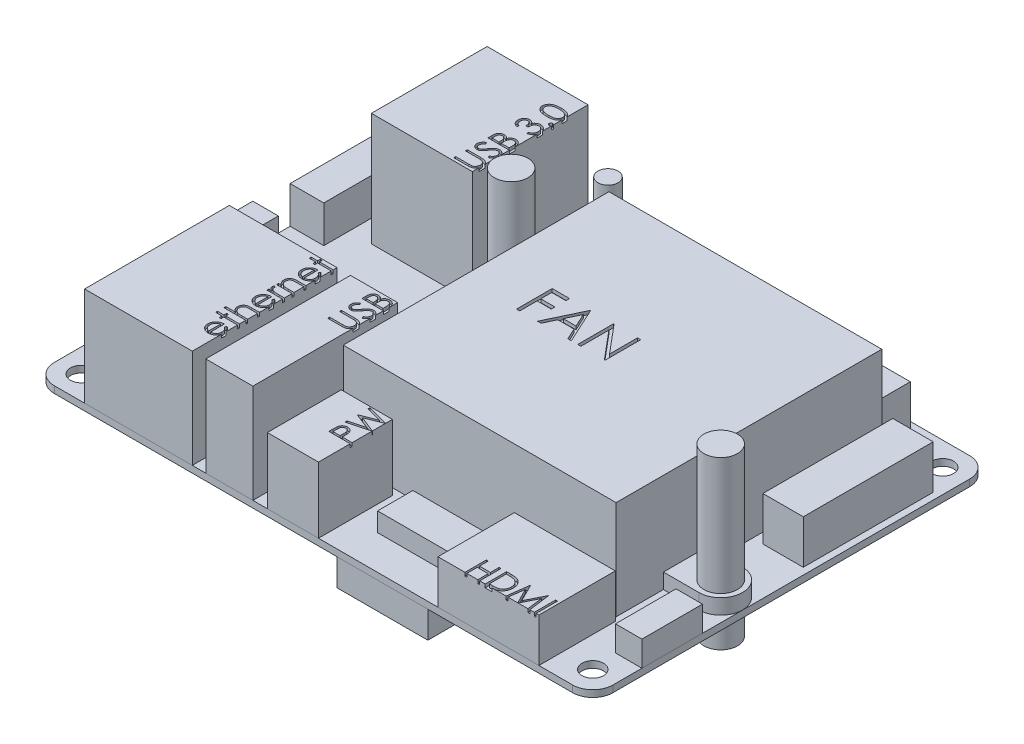
SolidWorks part; units mm, degrees
material "Silicon"
ref_plane "Front Plane" through (0, 0, 0) normal (0, 0, 1) x (1, 0, 0)
ref_plane "Top Plane" through (0, 0, 0) normal (0, 1, 0) x (1, 0, 0)
ref_plane "Right Plane" through (0, 0, 0) normal (1, 0, 0) x (0, 0, -1)
sketch "Sketch1" plane through (0, 0, 0) normal (0, 1, 0) x (1, 0, 0)
  line L1 (-38.5, -29.5) -> (38.5, -29.5)
  line L2 (-41.5, -26.5) -> (-41.5, 26.5)
  line L3 (-38.5, 29.5) -> (38.5, 29.5)
  line L4 (41.5, -26.5) -> (41.5, 26.5)
  line L5 (-41.5, -29.5) -> (41.5, 29.5) construction
  line L6 (-41.5, 29.5) -> (41.5, -29.5) construction
  arc A0 (38.5, 29.5) -> (41.5, 26.5) centre (38.5, 26.5) cw
  arc A1 (38.5, -29.5) -> (41.5, -26.5) centre (38.5, -26.5) ccw
  arc A2 (-38.5, -29.5) -> (-41.5, -26.5) centre (-38.5, -26.5) cw
  arc A3 (-41.5, 26.5) -> (-38.5, 29.5) centre (-38.5, 26.5) cw
  point P0 (0, 0)
  dimension "D3" = 3
  dimension "D1" = 83
  dimension "D2" = 59
extrude "PCB Extrude" add sketch "Sketch1" against normal blind 1
ref_plane "Plane_UnderSurface" through (0, -0.1, 0) normal (0, 1, 0) x (1, 0, 0)
ref_plane "Plane_AboveTop" through (0, 1, 0) normal (0, 1, 0) x (1, 0, 0)
sketch "IMAGE_TOP_PADS" plane through (0, 1, 0) normal (0, 1, 0) x (1, 0, 0)
  line L0 (-47.2752, 1.0682) -> (46.7248, 1.0682) construction
  line L2 (-41.5535, -29.5341) -> (41.4465, -29.5341) construction
  line L31 (-40.884, -25.1069) -> (-40.884, 27.8931) construction
  dimension "D1" = 53
  dimension "D2" = 83
sketch "IMAGE_TOP_COMPONENTS" plane through (0, 1, 0) normal (0, 1, 0) x (1, 0, 0)
  line L0 (-41.4491, -26.8822) -> (41.5509, -26.8822) construction
  dimension "D1" = 83
sketch "IMAGE_BOTTOM_COMPONENTS" plane through (0, -1, 0) normal (0, -1, 0) x (1, 0, 0)
  line L0 (-41.5726, -13.5939) -> (41.4274, -13.5939) construction
  dimension "D1" = 83
sketch "Sketch3" plane through (0, 0, 0) normal (0, 1, 0) x (1, 0, 0)
  line L0 (-38, -26) -> (38, -26) construction
  line L1 (-38, -26) -> (-38, 26) construction
  line L4 (38.5, 29.5) -> (-38.5, 29.5)
  line L5 (-41.5, 26.5) -> (-41.5, -26.5)
  line L6 (-38.5, -29.5) -> (38.5, -29.5)
  line L7 (41.5, -26.5) -> (41.5, 26.5)
  line L8 (38.5, 29.5) -> (-38.5, 29.5) construction
  line L9 (-41.5, 26.5) -> (-41.5, -26.5) construction
  line L10 (-38.5, -29.5) -> (38.5, -29.5) construction
  line L11 (41.5, -26.5) -> (41.5, 26.5) construction
  circle A0 centre (-12.8308, 12.7046) radius 1.6
  circle A1 centre (38.2313, -7.2227) radius 1.6
  circle A2 centre (-38, 26) radius 1.6
  circle A4 centre (38, 26) radius 1.6
  circle A6 centre (38, -26) radius 1.6
  arc A7 (41.5, 26.5) -> (38.5, 29.5) centre (38.5, 26.5) ccw
  circle A8 centre (-38, -26) radius 1.6
  arc A9 (-38.5, 29.5) -> (-41.5, 26.5) centre (-38.5, 26.5) ccw
  arc A10 (-41.5, -26.5) -> (-38.5, -29.5) centre (-38.5, -26.5) ccw
  arc A11 (38.5, -29.5) -> (41.5, -26.5) centre (38.5, -26.5) ccw
  arc A12 (41.5, 26.5) -> (38.5, 29.5) centre (38.5, 26.5) ccw construction
  arc A13 (-38.5, 29.5) -> (-41.5, 26.5) centre (-38.5, 26.5) ccw construction
  arc A14 (-41.5, -26.5) -> (-38.5, -29.5) centre (-38.5, -26.5) ccw construction
  arc A15 (38.5, -29.5) -> (41.5, -26.5) centre (38.5, -26.5) ccw construction
  point P0 (0, -26)
  point P6 (-38, 0)
  dimension "D1" = 3.2
  dimension "D2" = 52
  dimension "D3" = 76
  dimension "D4" = 0
extrude "PCB Holes and Tabs" cut sketch "Sketch3" against normal through all
sketch "Gross Components" plane through (-30.6818, 0, -29.2971) normal (0, 1, 0) x (1, 0, 0)
  line L0 (69.1818, 0.2029) -> (-7.8182, 0.2029) construction
  line L1 (15.4442, 0.2029) -> (21.4442, 0.2029)
  line L2 (15.4442, 0.2029) -> (15.4442, -5.7971)
  line L3 (15.4442, -5.7971) -> (21.4442, -5.7971)
  line L4 (21.4442, 0.2029) -> (21.4442, -5.7971)
  line L5 (-10.8182, -8.5628) -> (-10.8182, -20.7628)
  line L6 (-10.8182, -2.7971) -> (-10.8182, -55.7971) construction
  line L7 (-10.8182, -20.7628) -> (-5.8182, -20.7628)
  line L8 (-5.8182, -20.7628) -> (-5.8182, -9.977)
  line L9 (-5.8182, -9.977) -> (-7.2324, -8.5628)
  line L10 (-7.2324, -8.5628) -> (-10.8182, -8.5628)
  line L11 (72.1818, -55.7971) -> (72.1818, -2.7971) construction
  line L12 (-10.8182, -26.3049) -> (-7.0182, -26.3049)
  line L13 (-10.8182, -26.3049) -> (-10.8182, -33.6049)
  line L14 (-10.8182, -33.6049) -> (-7.0182, -33.6049)
  line L15 (-7.0182, -26.3049) -> (-7.0182, -33.6049)
  line L16 (19.72, -36.9097) -> (15.92, -36.9097)
  line L17 (19.72, -36.9097) -> (19.72, -29.6097)
  line L18 (19.72, -29.6097) -> (15.92, -29.6097)
  line L19 (15.92, -36.9097) -> (15.92, -29.6097)
  line L20 (35.097, -48.438) -> (46.497, -48.438)
  line L21 (35.097, -48.438) -> (35.097, -53.688)
  line L22 (35.097, -53.688) -> (46.497, -53.688)
  line L23 (46.497, -48.438) -> (46.497, -53.688)
  line L24 (72.1818, -42.4971) -> (68.2513, -42.4971)
  line L25 (72.1818, -42.4971) -> (72.1818, -51.4971)
  line L26 (72.1818, -51.4971) -> (68.2513, -51.4971)
  line L27 (68.2513, -42.4971) -> (68.2513, -51.4971)
  line L28 (68.9131, -39.7698) -> (63.6539, -39.7698)
  line L29 (23.1192, -46.8041) -> (63.6539, -46.8041)
  line L30 (23.1192, -46.8041) -> (23.1192, -7.329)
  line L31 (23.1192, -7.329) -> (63.6539, -7.329)
  line L32 (63.6539, -46.8041) -> (63.6539, -7.329)
  line L33 (23.8276, -47.8135) -> (31.4276, -47.8135)
  line L34 (23.8276, -47.8135) -> (23.8276, -58.7971)
  line L35 (23.8276, -58.7971) -> (31.4276, -58.7971)
  line L36 (31.4276, -47.8135) -> (31.4276, -58.7971)
  line L37 (68.9131, -33.2698) -> (63.6539, -33.2698)
  line L38 (17.851, -19.8425) -> (23.1192, -19.8425)
  line L39 (17.851, -13.3425) -> (23.1192, -13.3425)
  line L40 (-2.5182, 0.2029) -> (-2.5182, -16.9903)
  line L41 (-2.5182, -16.9903) -> (12.4818, -16.9903)
  line L42 (12.4818, -16.9903) -> (12.4818, 0.2029)
  line L43 (12.4818, 0.2029) -> (-2.5182, 0.2029)
  line L44 (-3.3182, -58.7971) -> (-3.3182, -37.2971)
  line L45 (-7.8182, -58.7971) -> (69.1818, -58.7971) construction
  line L46 (-3.3182, -37.2971) -> (12.6818, -37.2971)
  line L47 (12.6818, -37.2971) -> (12.6818, -58.7971)
  line L48 (12.6818, -58.7971) -> (-3.3182, -58.7971)
  line L49 (14.6818, -58.7971) -> (14.6818, -37.2971)
  line L50 (14.6818, -37.2971) -> (21.6818, -37.2971)
  line L51 (21.6818, -37.2971) -> (21.6818, -58.7971)
  line L52 (21.6818, -58.7971) -> (14.6818, -58.7971)
  line L53 (49.1818, -58.7971) -> (49.1818, -47.4469)
  line L54 (49.1818, -47.4469) -> (64.1818, -47.4469)
  line L55 (64.1818, -47.4469) -> (64.1818, -58.7971)
  line L56 (64.1818, -58.7971) -> (49.1818, -58.7971)
  line L57 (24.4567, -7.1971) -> (24.4567, -1.1971)
  line L58 (24.4567, -1.1971) -> (61.7567, -1.1971)
  line L59 (61.7567, -1.1971) -> (61.7567, -7.1971)
  line L60 (61.7567, -7.1971) -> (24.4567, -7.1971)
  line L61 (65.1818, -7.2218) -> (65.1818, -26.5218)
  line L62 (65.1818, -26.5218) -> (71.1818, -26.5218)
  line L63 (71.1818, -26.5218) -> (71.1818, -7.2218)
  line L64 (71.1818, -7.2218) -> (65.1818, -7.2218)
  arc A0 (17.851, -13.3425) -> (17.851, -19.8425) centre (17.851, -16.5925) ccw
  arc A1 (68.9131, -39.7698) -> (68.9131, -33.2698) centre (68.9131, -36.5198) ccw
  circle A2 centre (17.851, -16.5925) radius 1.6 construction
  circle A3 centre (17.851, -16.5925) radius 1.6
  circle A4 centre (68.9131, -36.5198) radius 1.6 construction
  circle A5 centre (68.9131, -36.5198) radius 1.6
  circle M1 centre (68.9131, -36.5198) radius 1.6
  circle M2 centre (17.851, -16.5925) radius 1.6
  line M10 (-10.8182, -2.7971) -> (-10.8182, -55.7971)
  line M12 (-7.8182, -58.7971) -> (69.1818, -58.7971)
  line M14 (72.1818, -55.7971) -> (72.1818, -2.7971)
  dimension "D1" = 3.25
  dimension "D2" = 3.25
  dimension "D3" = 12.2
  dimension "D4" = 5
  dimension "D5" = 7.3
  dimension "D6" = 3.8
  dimension "D7" = 15
  dimension "D8" = 7.6
  dimension "D9" = 8.3
  dimension "D10" = 6
  dimension "D11" = 6
  dimension "D12" = 16
  dimension "D13" = 21.5
  dimension "D14" = 7.5
  dimension "D15" = 2
  dimension "D16" = 7
  dimension "D17" = 21.5
  dimension "D18" = 15
  dimension "D19" = 8
  dimension "D20" = 11.4
  dimension "D21" = 5.25
  dimension "D22" = 2
  dimension "D23" = 37.3
  dimension "D24" = 1.4
  dimension "D25" = 6
  dimension "D26" = 6
  dimension "D27" = 19.3
  dimension "D28" = 7.3
  dimension "D29" = 9
  dimension "D30" = 1
  dimension "D31" = 45
extrude "UART Extrude" add sketch "Gross Components" along normal blind 5.5 contours L9 L10 L7 L8 M10 region at (-39.0338, 0, -14.5405)
extrude "Battery and Fan Header" add sketch "Sketch4<3>" along normal blind 6 contours L15 L12 L14 M10 | L19 L18 L17 L16 region at (-39.6, 0, 0.6578)
sketch "Sketch4<3>" plane through (-30.6818, 0, -29.2971) normal (0, 1, 0) x (1, 0, 0) same geometry as "Gross Components"
extrude "HeatSink_Fan" add sketch "Sketch4<4>" along normal blind 14.7 contours L29 L32 L31 L30 region at (12.7048, 0, -2.2305)
sketch "Sketch4<4>" plane through (-30.6818, 0, -29.2971) normal (0, 1, 0) x (1, 0, 0) same geometry as "Gross Components"
extrude "PowerButton" add sketch "Sketch4<6>" along normal blind 3.5 contours L3 L4 L1 L2
sketch "Sketch4<6>" plane through (-30.6818, 0, -29.2971) normal (0, 1, 0) x (1, 0, 0) same geometry as "Gross Components"
sketch "Sketch5" plane through (0, 3.5, 0) normal (0, 1, 0) x (1, 0, 0)
  line L0 (-15.2376, 29.5) -> (-9.2376, 23.5) construction
  circle A0 centre (-12.2376, 26.5) radius 1.5
  dimension "D1" = 3
extrude "PowerButtonSwitch" add sketch "Sketch5" along normal blind 8.5
extrude "DCPowerJack" add sketch "Sketch4<8>" along normal blind 9.8 contours L35 L36 L33 L34
sketch "Sketch4<8>" plane through (-30.6818, 0, -29.2971) normal (0, 1, 0) x (1, 0, 0) same geometry as "Gross Components"
extrude "HeatSinkMountTabs" add sketch "Sketch4<11>" along normal blind 2.25 contours L39 A0 L38 L30 M2 | L28 A1 L37 L32 M14 M1 region at (35.6017, 0, 10.3656) region at (-10.1967, 0, -9.5618)
sketch "Sketch4<11>" plane through (-30.6818, 0, -29.2971) normal (0, 1, 0) x (1, 0, 0) same geometry as "Gross Components"
sketch "Sketch6" plane through (0, 2.25, 0) normal (0, 1, 0) x (1, 0, 0)
  circle A0 centre (38.2313, -7.2227) radius 2.5
  circle A1 centre (-12.8308, 12.7046) radius 2.5
  dimension "D1" = 5
extrude "HeatSinkSprings" add sketch "Sketch6" along normal blind 17.5
extrude "microSD" add sketch "Sketch4<13>" along normal blind 2.8 contours L22 L23 L20 L21
sketch "Sketch4<13>" plane through (-30.6818, 0, -29.2971) normal (0, 1, 0) x (1, 0, 0) same geometry as "Gross Components"
sketch "Sketch7" plane through (0, -1, 0) normal (0, -1, 0) x (1, 0, 0)
  line L0 (17, 29.5) -> (17, 11)
  line L1 (-38.5, 29.5) -> (38.5, 29.5) construction
  line L2 (17, 11) -> (3.5, 11)
  line L3 (3.5, 11) -> (3.5, 29.5)
  line L4 (3.5, 29.5) -> (17, 29.5)
  line L5 (41.5, 26.5) -> (41.5, -26.5) construction
  circle A0 centre (-12.8308, -12.7046) radius 2.5
  circle A1 centre (38.2313, 7.2227) radius 2.5
  dimension "D4" = 5
  dimension "D1" = 18.5
  dimension "D2" = 13.5
  dimension "D3" = 24.5
extrude "UnderSide" add sketch "Sketch7" along normal blind 4
extrude "Ethernet" add sketch "Gross Components<15>" along normal blind 14.7 contours L47 L46 L44 M12 region at (-26, 0, 18.75)
sketch "Gross Components<15>" plane through (-30.6818, 0, -29.2971) normal (0, 1, 0) x (1, 0, 0) same geometry as "Gross Components"
extrude "USBx2" add sketch "Gross Components<16>" along normal blind 16.8 contours L41 L42 L43 L40
sketch "Gross Components<16>" plane through (-30.6818, 0, -29.2971) normal (0, 1, 0) x (1, 0, 0) same geometry as "Gross Components"
extrude "USBvertical" add sketch "Gross Components<17>" along normal blind 14.7 contours L51 L52 L49 L50
sketch "Gross Components<17>" plane through (-30.6818, 0, -29.2971) normal (0, 1, 0) x (1, 0, 0) same geometry as "Gross Components"
extrude "HDMI" add sketch "Gross Components<18>" along normal blind 6.5 contours L53 L54 L55 L56
sketch "Gross Components<18>" plane through (-30.6818, 0, -29.2971) normal (0, 1, 0) x (1, 0, 0) same geometry as "Gross Components"
extrude "DIP" add sketch "Gross Components<19>" along normal blind 3.75 contours L26 L27 L24 L25
sketch "Gross Components<19>" plane through (-30.6818, 0, -29.2971) normal (0, 1, 0) x (1, 0, 0) same geometry as "Gross Components"
extrude "PinHeaders" add sketch "Gross Components<21>" along normal blind 6.5 contours L60 L59 L58 L57 | L63 L64 L61 L62 region at (12.4249, 0, -25.1) region at (37.5, 0, -12.4253)
sketch "Gross Components<21>" plane through (-30.6818, 0, -29.2971) normal (0, 1, 0) x (1, 0, 0) same geometry as "Gross Components"
sketch "Sketch9" plane through (0, 0, 29.5) normal (0, 0, 1) x (1, 0, 0)
  line L0 (-72.0907, 0) -> (76.0017, 0)
  line L1 (-38.5, 0) -> (-34, 0) construction
split line "SplitLine_TopPCB"
sketch "Sketch10" plane through (0, 0, 29.5) normal (0, 0, 1) x (1, 0, 0)
  line L0 (-60.8959, -1) -> (56.8491, -1)
  line L1 (-38.5, -1) -> (3.5, -1) construction
split line "SplitLine_BottomPCB"
sketch "Sketch11" plane through (0, 14.7, 0) normal (0, 1, 0) x (1, 0, 0)
  text T0 "FAN" font "Century Gothic" height in points 20
sketch "Sketch12" plane through (0, 6.5, 0) normal (0, 1, 0) x (1, 0, 0)
  text T0 "HDMI"
sketch "Sketch13" plane through (0, 9.8, 0) normal (0, 1, 0) x (1, 0, 0)
  text T0 "PW"
sketch "Sketch14" plane through (0, 14.7, 0) normal (0, 1, 0) x (1, 0, 0)
  text T0 "USB"
sketch "Sketch15" plane through (0, 14.7, 0) normal (0, 1, 0) x (1, 0, 0)
  text T0 "ethernet"
sketch "Sketch16" plane through (0, 16.8, 0) normal (0, 1, 0) x (1, 0, 0)
  text T0 "USB 3.0"
extrude "Cut-Extrude1" cut sketch "Sketch11" against normal blind 0.5
extrude "Cut-Extrude2" cut sketch "Sketch13" against normal blind 0.5
extrude "Cut-Extrude3" cut sketch "Sketch12" against normal blind 0.5
extrude "Cut-Extrude4" cut sketch "Sketch14" against normal blind 0.5
extrude "Cut-Extrude5" cut sketch "Sketch15" against normal blind 0.5
extrude "Cut-Extrude6" cut sketch "Sketch16" against normal blind 0.5
sketch "Sketch21" plane through (0, -1, 0) normal (0, -1, 0) x (1, 0, 0)
  line L0 (1.5, -25.5) -> (1.5, -35.4955)
  line L1 (1.5, -25.5) -> (0.6896, -25.5)
  line L2 (1.5, -35.4955) -> (0.6896, -35.4955)
  line L3 (0.6896, -25.5) -> (0.6896, -35.4955)
  line L4 (41.5, 26.5) -> (41.5, -26.5) construction
  line L5 (38.5, -29.5) -> (-38.5, -29.5) construction
  dimension "D1" = 40
  dimension "D2" = 4
extrude "Cut-Extrude7" cut sketch "Sketch21" against normal blind 1
